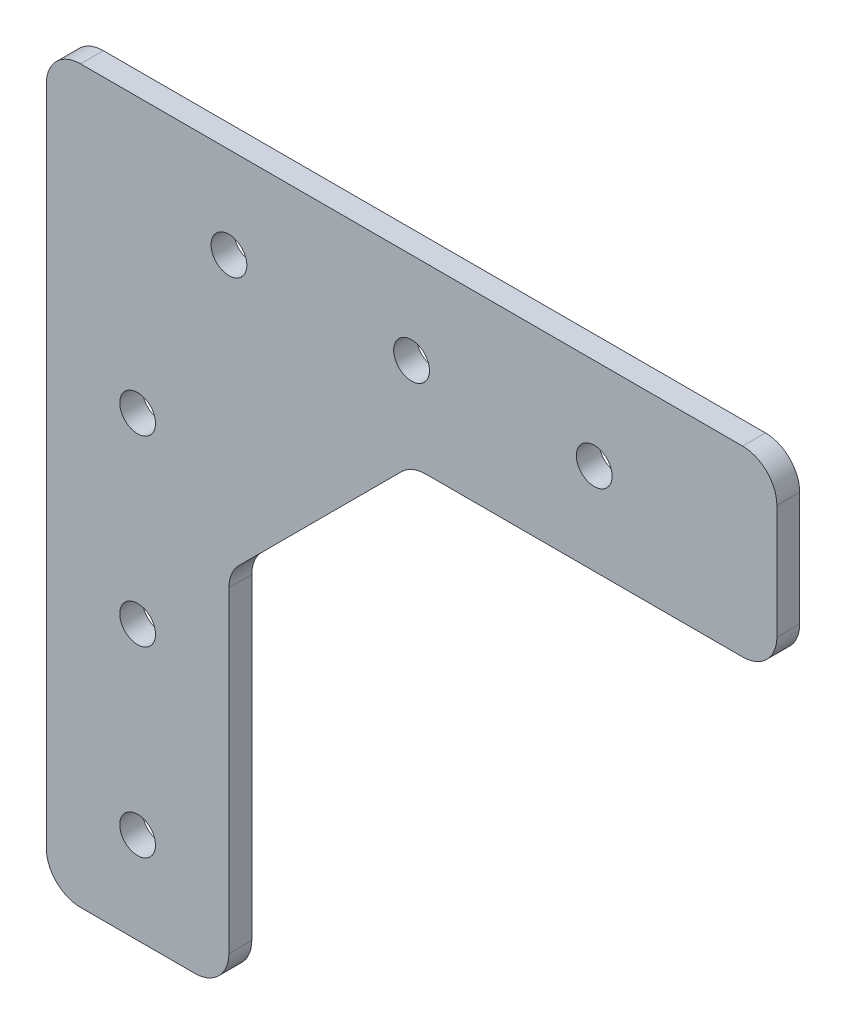
SolidWorks part; units mm, degrees
material "6061-T6 (SS)"
ref_plane "Front Plane" through (0, 0, 0) normal (0, 0, 1) x (1, 0, 0)
ref_plane "Top Plane" through (0, 0, 0) normal (0, 1, 0) x (1, 0, 0)
ref_plane "Right Plane" through (0, 0, 0) normal (1, 0, 0) x (0, 0, -1)
sketch "Sketch1" plane through (0, 0, 0) normal (0, 0, 1) x (1, 0, 0)
  line L8 (0, 0) -> (0, 101.6)
  line L14 (0, 101.6) -> (101.6, 101.6)
  line L15 (101.6, 101.6) -> (101.6, 76.2)
  line L17 (25.4, 0) -> (0, 0)
  line L18 (12.7, 0) -> (12.7, 101.6) construction
  line L19 (25.4, 0) -> (25.4, 50.8)
  line L20 (25.4, 50.8) -> (50.8, 76.2)
  line L21 (50.8, 76.2) -> (101.6, 76.2)
  circle A7 centre (12.7, 63.5) radius 2.4892
  circle A8 centre (12.7, 38.1) radius 2.4892
  circle A9 centre (12.7, 12.7) radius 2.4892
  circle A11 centre (76.2, 88.9) radius 2.4892
  circle A12 centre (50.8, 88.9) radius 2.4892
  circle A13 centre (25.4, 88.9) radius 2.4892
  point P21 (28.5138, 46.4488)
  point P22 (101.6, 76.2)
  point P23 (0, 0)
  point P24 (54.0871, 76.2)
  point P28 (69.9071, 88.9)
  point P29 (45.1832, 76.2)
  dimension "D5" = 4.9784
  dimension "D7" = 12.7
  dimension "D1" = 25.4
  dimension "D2" = 101.6
  dimension "D3" = 101.6
  dimension "D4" = 3
  dimension "D6" = 25.4
  dimension "D8" = 3
  dimension "D9" = 12.7
  dimension "D10" = 25.4
  dimension "D11" = 25.4
  dimension "D12" = 50.8
extrude "Boss-Extrude1" add sketch "Sketch1" along normal mid plane 3.175 contours L18 A7 | A7 L18 | L18 A9 | A9 L18 | A11 | L8 L14 L15 L21 L20 L19 L17 | A8 | A12 | A13 region at (11.6436, 12.7, 0) region at (13.7564, 12.7, 0) region at (13.7564, 63.5, 0) region at (11.6436, 63.5, 0) region at (76.2, 88.9, 0)
fillet "Fillet1" radius 4.7625 7 edges at (0, 101.6, 0) (0, 0, 0) (101.6, 76.2, 0) (50.8, 76.2, 0) (25.4, 50.8, 0) (25.4, 0, 0) (101.6, 101.6, 0)
